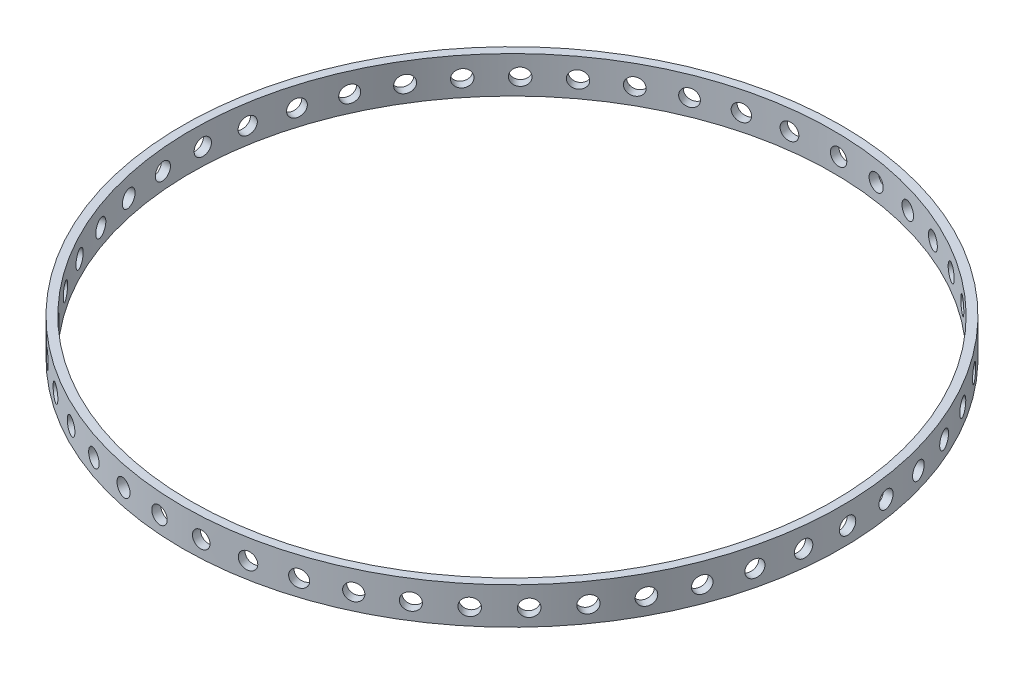
SolidWorks part; units mm, degrees
material "ABS PC"
ref_plane "Front" through (0, 0, 0) normal (0, 0, 1) x (1, 0, 0)
ref_plane "Top" through (0, 0, 0) normal (0, 1, 0) x (1, 0, 0)
ref_plane "Right" through (0, 0, 0) normal (1, 0, 0) x (0, 0, -1)
sketch "Sketch1" plane through (0, 0, 0) normal (0, 1, 0) x (1, 0, 0)
  circle A0 centre (0, 0) radius 96
  circle A1 centre (0, 0) radius 98.5
  dimension "D1" = 2.5
  dimension "D2" = 192
extrude "Boss-Extrude1" add sketch "Sketch1" along normal blind 11
sketch "Sketch2" plane through (0, 0, 0) normal (0, 0, 1) x (1, 0, 0)
  line L0 (0, 0) -> (0, 5) construction
  circle A0 centre (0, 5) radius 2.5
  dimension "D2" = 5
  dimension "D1" = 5
extrude "Cut-Extrude1" cut sketch "Sketch2" against normal blind 500
pattern_circular "CirPattern9" count 50 over 359 about axis through (0, 11, 0) along (0, 1, 0) of "Cut-Extrude1", "Boss-Extrude1"
